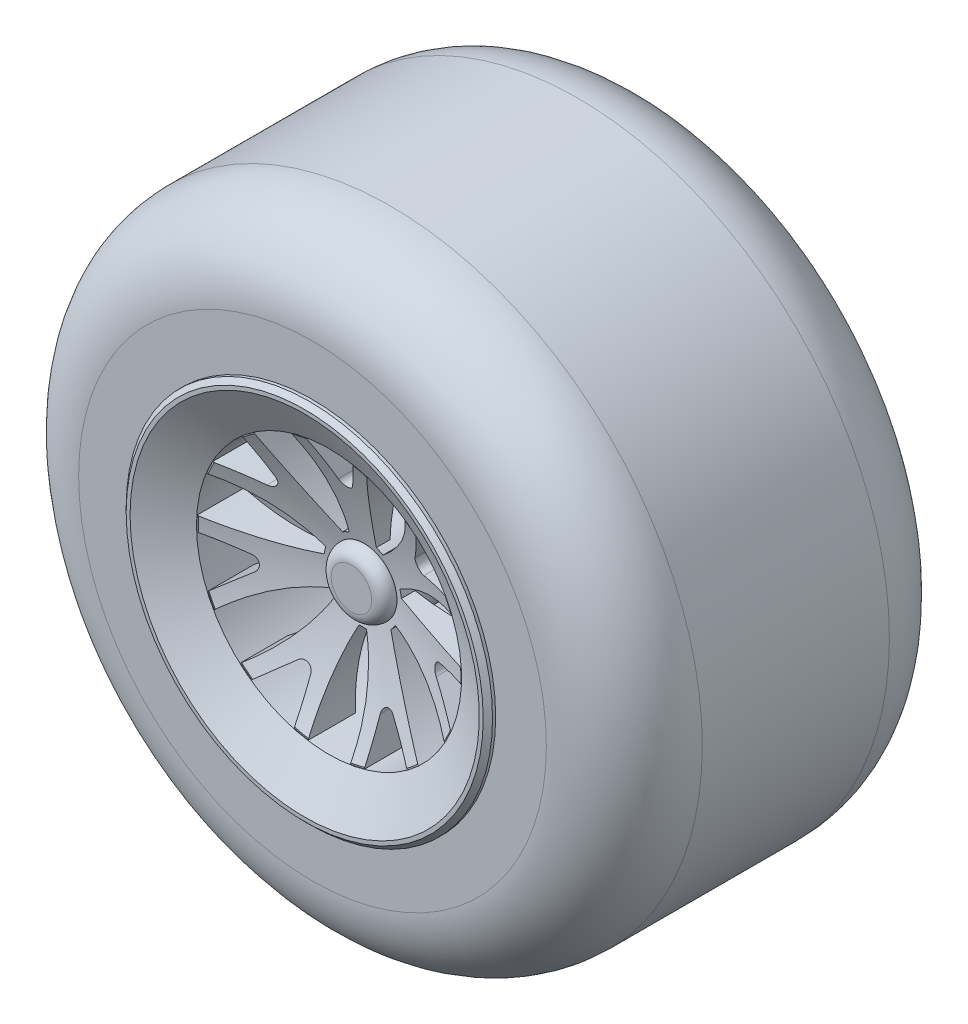
SolidWorks part; units mm, degrees
ref_plane "Front Plane" through (0, 0, 0) normal (0, 0, 1) x (1, 0, 0)
ref_plane "Top Plane" through (0, 0, 0) normal (0, 1, 0) x (1, 0, 0)
ref_plane "Right Plane" through (0, 0, 0) normal (1, 0, 0) x (0, 0, -1)
sketch "Sketch1" plane through (0, 0, 0) normal (1, 0, 0) x (0, 0, -1)
  line L0 (0, 0) -> (23, 0) construction
  line L1 (0, 0) -> (0, 11.75)
  line L2 (0, 11.75) -> (0.5, 11.75)
  line L3 (0.5, 11.75) -> (0.5, 15)
  line L4 (5.5, 20) -> (17.5, 20)
  line L5 (22.5, 15) -> (22.5, 11.75)
  line L6 (22.5, 11.75) -> (23, 11.75)
  line L7 (23, 11.75) -> (23, 0)
  line L8 (23, 0) -> (0, 0)
  arc A0 (17.5, 20) -> (22.5, 15) centre (17.5, 15) cw
  arc A1 (0.5, 15) -> (5.5, 20) centre (5.5, 15) cw
  dimension "D6" = 5
  dimension "D1" = 23
  dimension "D2" = 11.75
  dimension "D3" = 20
  dimension "D4" = 0.5
  dimension "D5" = 0.5
  dimension "D7" = 11.75
revolve "Revolve1" add sketch "Sketch1" angle 360 about L0
sketch "Sketch2" plane through (0, 0, 0) normal (0, 0, 1) x (1, 0, 0)
  circle A0 centre (0, 0) radius 2.5
  circle A1 centre (0, 0) radius 8.5
  dimension "D1" = 5
  dimension "D2" = 17
extrude "Cut-Extrude1" cut sketch "Sketch2" against normal through all
chamfer "Chamfer1" distance 0.3 angle 45 1 edges at (11.75, 0, 0)
chamfer "Chamfer2" distance 0.3 angle 45 1 edges at (11.75, 0, -23)
chamfer "Chamfer3" distance 2.7 angle 30 1 edges at (8.5, 0, 0) first distance on face at (-11.45, 0, 0)
sketch "Sketch3" plane through (0, 0, 0) normal (0, 0, 1) x (1, 0, 0)
  line L0 (0, 0) -> (0, 10.6863) construction
  line L1 (-3.5089, 9.8628) -> (-2.2326, 9.8628)
  line L2 (2.2326, 9.8628) -> (3.5089, 9.8628)
  line L3 (-0.8606, 1.7264) -> (0.8606, 1.7264)
  line L4 (0.8132, 1.7492) -> (1.8863, 0.4036)
  line L5 (5.5233, 8.8927) -> (6.3191, 7.8949)
  line L6 (9.1031, 4.4038) -> (9.8988, 3.406)
  line L7 (1.8746, 0.4548) -> (1.4916, -1.2232)
  line L8 (10.3963, 1.2263) -> (10.1123, -0.0181)
  line L9 (9.1187, -4.3713) -> (8.8347, -5.6156)
  line L10 (1.5244, -1.182) -> (-0.0263, -1.9288)
  line L11 (7.4407, -7.3636) -> (6.2908, -7.9174)
  line L12 (2.2678, -9.8548) -> (1.1179, -10.4086)
  line L13 (0.0263, -1.9288) -> (-1.5244, -1.182)
  line L14 (-1.1179, -10.4086) -> (-2.2678, -9.8548)
  line L15 (-6.2908, -7.9174) -> (-7.4407, -7.3636)
  line L16 (-1.4916, -1.2232) -> (-1.8746, 0.4548)
  line L17 (-8.8347, -5.6156) -> (-9.1187, -4.3713)
  line L18 (-10.1123, -0.0181) -> (-10.3963, 1.2263)
  line L19 (-1.8863, 0.4036) -> (-0.8132, 1.7492)
  line L20 (-9.8988, 3.406) -> (-9.1031, 4.4038)
  line L21 (-6.3191, 7.8949) -> (-5.5233, 8.8927)
  arc A0 (-3.5089, 9.8628) -> (-0.8606, 1.7264) centre (-14.2465, 1.8686) cw
  arc A1 (3.5089, 9.8628) -> (0.8606, 1.7264) centre (14.2465, 1.8686) ccw
  arc A2 (5.5233, 8.8927) -> (0.8132, 1.7492) centre (-7.4216, 12.3034) cw
  arc A3 (9.8988, 3.406) -> (1.8863, 0.4036) centre (10.3435, -9.9733) ccw
  arc A4 (10.3963, 1.2263) -> (1.8746, 0.4548) centre (4.9919, 13.4735) cw
  arc A5 (8.8347, -5.6156) -> (1.4916, -1.2232) centre (-1.3484, -14.3051) ccw
  arc A6 (7.4407, -7.3636) -> (1.5244, -1.182) centre (13.6464, 4.4978) cw
  arc A7 (1.1179, -10.4086) -> (-0.0263, -1.9288) centre (-12.0249, -7.8649) ccw
  arc A8 (-1.1179, -10.4086) -> (0.0263, -1.9288) centre (12.0249, -7.8649) cw
  arc A9 (-7.4407, -7.3636) -> (-1.5244, -1.182) centre (-13.6464, 4.4978) ccw
  arc A10 (-8.8347, -5.6156) -> (-1.4916, -1.2232) centre (1.3484, -14.3051) cw
  arc A11 (-10.3963, 1.2263) -> (-1.8746, 0.4548) centre (-4.9919, 13.4735) ccw
  arc A12 (-9.8988, 3.406) -> (-1.8863, 0.4036) centre (-10.3435, -9.9733) cw
  arc A13 (-5.5233, 8.8927) -> (-0.8132, 1.7492) centre (7.4216, 12.3034) ccw
  arc A14 (-4.4654, 4.1399) -> (-5.0297, 3.4322) centre (-4.9137, 3.9186) cw
  arc A15 (-6.0208, -0.91) -> (-5.8194, -1.7925) centre (-6.1273, -1.3985) cw
  arc A16 (-3.0425, -5.2746) -> (-2.2269, -5.6674) centre (-2.7269, -5.6625) cw
  arc A17 (2.2269, -5.6674) -> (3.0425, -5.2746) centre (2.7269, -5.6625) cw
  arc A18 (5.8194, -1.7925) -> (6.0208, -0.91) centre (6.1273, -1.3985) cw
  arc A19 (5.0297, 3.4322) -> (4.4654, 4.1399) centre (4.9137, 3.9186) cw
  arc A20 (-0.4526, 6.0723) -> (0.4526, 6.0723) centre (0, 6.2849) ccw
  spline S0 degree 3 poles (-2.2326, 9.8628) (-1.6393, 8.5993) (-1.0459, 7.3358) (-0.4526, 6.0723) knots 0 0 0 0 0.797286 0.797286 0.797286 0.797286
  spline S1 degree 3 poles (2.2326, 9.8628) (1.6393, 8.5993) (1.0459, 7.3358) (0.4526, 6.0723) knots 0 0 0 0 0.797286 0.797286 0.797286 0.797286
  spline S2 degree 3 poles (9.1031, 4.4038) (7.7453, 4.08) (6.3875, 3.7561) (5.0297, 3.4322) knots 0 0 0 0 0.797286 0.797286 0.797286 0.797286
  spline S3 degree 3 poles (6.3191, 7.8949) (5.7012, 6.6432) (5.0833, 5.3916) (4.4654, 4.1399) knots 0 0 0 0 0.797286 0.797286 0.797286 0.797286
  spline S4 degree 3 poles (9.1187, -4.3713) (8.019, -3.5117) (6.9192, -2.6521) (5.8194, -1.7925) knots 0 0 0 0 0.797286 0.797286 0.797286 0.797286
  spline S5 degree 3 poles (10.1123, -0.0181) (8.7485, -0.3154) (7.3847, -0.6127) (6.0208, -0.91) knots 0 0 0 0 0.797286 0.797286 0.797286 0.797286
  spline S6 degree 3 poles (2.2678, -9.8548) (2.2542, -8.459) (2.2406, -7.0632) (2.2269, -5.6674) knots 0 0 0 0 0.797286 0.797286 0.797286 0.797286
  spline S7 degree 3 poles (6.2908, -7.9174) (5.208, -7.0365) (4.1252, -6.1556) (3.0425, -5.2746) knots 0 0 0 0 0.797286 0.797286 0.797286 0.797286
  spline S8 degree 3 poles (-6.2908, -7.9174) (-5.208, -7.0365) (-4.1252, -6.1556) (-3.0425, -5.2746) knots 0 0 0 0 0.797286 0.797286 0.797286 0.797286
  spline S9 degree 3 poles (-2.2678, -9.8548) (-2.2542, -8.459) (-2.2406, -7.0632) (-2.2269, -5.6674) knots 0 0 0 0 0.797286 0.797286 0.797286 0.797286
  spline S10 degree 3 poles (-10.1123, -0.0181) (-8.7485, -0.3154) (-7.3847, -0.6127) (-6.0208, -0.91) knots 0 0 0 0 0.797286 0.797286 0.797286 0.797286
  spline S11 degree 3 poles (-9.1187, -4.3713) (-8.019, -3.5117) (-6.9192, -2.6521) (-5.8194, -1.7925) knots 0 0 0 0 0.797286 0.797286 0.797286 0.797286
  spline S12 degree 3 poles (-6.3191, 7.8949) (-5.7012, 6.6432) (-5.0833, 5.3916) (-4.4654, 4.1399) knots 0 0 0 0 0.797286 0.797286 0.797286 0.797286
  spline S13 degree 3 poles (-9.1031, 4.4038) (-7.7453, 4.08) (-6.3875, 3.7561) (-5.0297, 3.4322) knots 0 0 0 0 0.797286 0.797286 0.797286 0.797286
  point P68 (0, 0)
  circle M51 centre (0, 0) radius 2.5
  dimension "D2" = 0.5
  dimension "D1" = 7
extrude "Boss-Extrude1" add sketch "Sketch3" against normal blind 3 from offset 1.6 contours S3 L5 A2 A3 L6 S2 A19 M51 | L0 A1 L2 S1 A20 M51 | L0 A20 S0 L1 A0 M51 | S9 L14 A8 A9 L15 S8 A16 M51 | S7 L11 A6 A7 L12 S6 A17 M51 | S5 L8 A4 A5 L9 S4 A18 M51 | A13 L19 A12 L20 S13 A14 S12 L21 | S11 A15 S10 L18 A11 L16 A10 L17 region at (-1.2443, 6.2181, 0) region at (1.2443, 6.2181, 0) region at (4.0217, 5.1317, 0) region at (6.5184, 0.0658, 0) region at (-1.1336, -2.354, 0) region at (4.112, -5.0589, 0) offset against normal yes
sketch "Sketch4" plane through (0, 0, 0) normal (1, 0, 0) x (0, 0, -1)
  line L0 (-3.3716, 0) -> (25.2555, 0) construction
  line L2 (1.5591, 8.5) -> (-2.971, 8.5)
  line L3 (-2.971, 8.5) -> (-2.971, 0)
  line L4 (-2.971, 0) -> (4.1928, 0)
  spline S0 degree 2 poles (1.5591, 8.5) (3.6082, 4.3057) (4.1928, 0) knots 0 0 0 1 1 1
  dimension "D1" = 8.5
revolve "Cut-Revolve1" cut sketch "Sketch4" angle 360 about L4
sketch "Sketch5" plane through (0, 0, 0) normal (0, 0, 1) x (1, 0, 0)
  circle A0 centre (0, 0) radius 2.1
  dimension "D1" = 4.2
extrude "Boss-Extrude2" add sketch "Sketch5" along normal blind 1 from offset 4 offset against normal yes
fillet "Fillet1" radius 0.8 1 edges at (2.1, 0, -3)
ref_plane "Plane1" through (0, 0, -11.5) normal (0, 0, 1) x (1, 0, 0)
sketch "Sketch8" plane through (0, 0, 0) normal (0, 1, 0) x (1, 0, 0)
  line L0 (-22, 11.5) -> (22, 11.5) construction
  line L1 (-25.922, 27.7457) -> (22.6017, 27.7457)
  line L2 (-25.922, 27.7457) -> (-25.922, 11.5)
  line L3 (-25.922, 11.5) -> (22.6017, 11.5)
  line L4 (22.6017, 27.7457) -> (22.6017, 11.5)
extrude "Cut-Extrude2" cut sketch "Sketch8" against normal through all both and the other way through all
mirror "Mirror3" about plane through (0, 0, -11.5) normal (0, 0, 1) of bodies 108
sketch "Sketch9" plane through (0, 0, -11.5) normal (0, 0, 1) x (1, 0, 0)
  circle A0 centre (0, 0) radius 2.1
extrude "Cut-Extrude3" cut sketch "Sketch9" against normal blind 17 from offset 5 offset against normal yes
